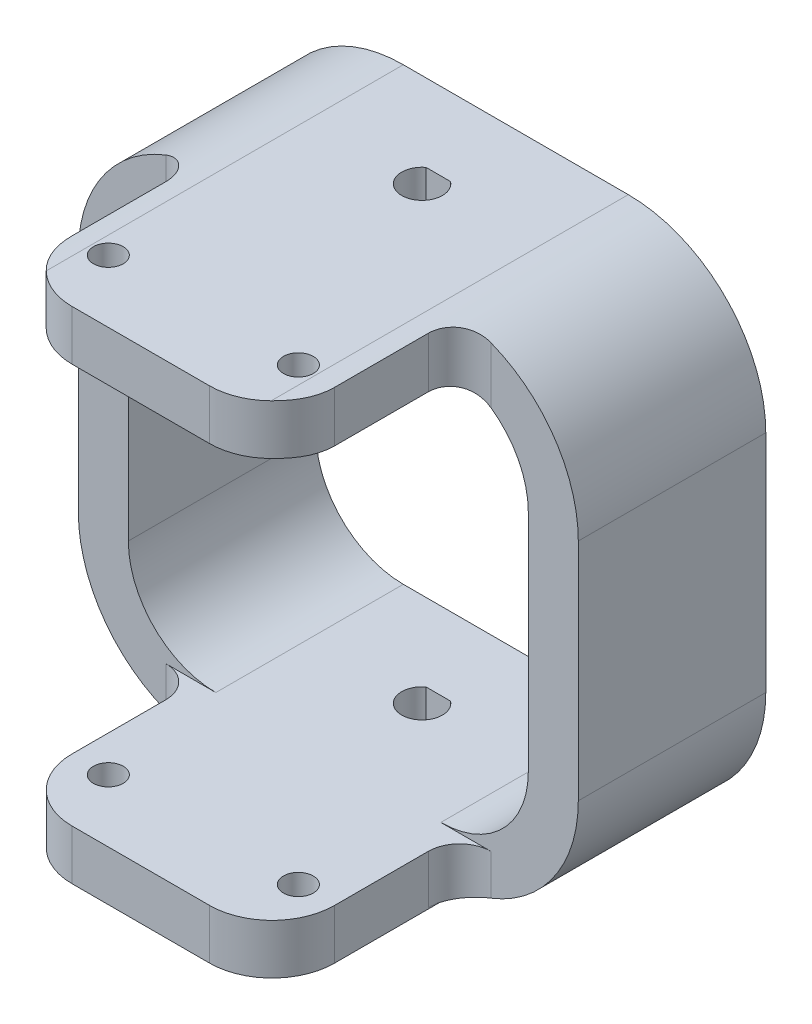
SolidWorks part; units mm, degrees
material "Plastique personnalisé"
ref_plane "Plan de face" through (0, 0, 0) normal (0, 0, 1) x (1, 0, 0)
ref_plane "Plan de dessus" through (0, 0, 0) normal (0, 1, 0) x (1, 0, 0)
ref_plane "Plan de droite" through (0, 0, 0) normal (1, 0, 0) x (0, 0, -1)
sketch "Esquisse1" plane through (0, 0, 0) normal (0, 0, 1) x (1, 0, 0)
  line L1 (40, -40) -> (-40, -40)
  line L2 (40, -40) -> (40, 40)
  line L3 (40, 40) -> (-40, 40)
  line L4 (-40, -40) -> (-40, 40)
  line L5 (40, -40) -> (-40, 40) construction
  line L6 (40, 40) -> (-40, -40) construction
  line L7 (-32, -32) -> (32, -32)
  line L8 (-32, -32) -> (-32, 32)
  line L9 (-32, 32) -> (32, 32)
  line L10 (32, -32) -> (32, 32)
  line L11 (-32, -32) -> (32, 32) construction
  line L12 (-32, 32) -> (32, -32) construction
  point P0 (0, 0)
  point P11 (0, 0)
  dimension "D1" = 8
  dimension "D3" = 80
extrude "Boss.-Extru.1" add sketch "Esquisse1" along normal mid plane 30
sketch "Esquisse2" plane through (0, 0, 0) normal (1, 0, 0) x (0, 0, -1)
  circle A0 centre (0, 0) radius 5
  dimension "D1" = 10
extrude "Enlèv. mat.-Extru.1" [suppressed] cut sketch "Esquisse2" against normal through all both and the other way through all
sketch "Esquisse3" plane through (0, -40, 0) normal (0, -1, 0) x (-1, 0, 0)
  circle A0 centre (0, 0) radius 5
  dimension "D1" = 10
extrude "Boss.-Extru.2" [suppressed] add sketch "Esquisse3" along normal blind 20
mirror "Symétrie1" [suppressed] about plane through (0, 0, 0) normal (0, 1, 0)
sketch "Esquisse7" plane through (0, 0, 15) normal (0, 0, 1) x (1, 0, 0)
  line L0 (40, 40) -> (-40, 40) construction
  line L1 (21, 32) -> (-21, 32)
  line L2 (21, 32) -> (21, 40)
  line L3 (21, 40) -> (-21, 40)
  line L4 (-21, 32) -> (-21, 40)
  line L5 (40, 40) -> (-40, 40) construction
  line L6 (32, 32) -> (-32, 32) construction
  point P10 (0, 40)
  point P11 (0, 40)
  dimension "D1" = 42
extrude "Boss.-Extru.4" add sketch "Esquisse7" along normal blind 30
fillet "Congé2" radius 22 4 edges at (40, -40, 0) (-40, -40, 0) (-40, 40, 0) (40, 40, 0)
fillet "Congé3" radius 14 4 edges at (-32, 32, 0) (-32, -32, 0) (32, -32, 0) (32, 32, 0)
sketch "Esquisse5" [suppressed] plane through (0, -60, 0) normal (0, -1, 0) x (1, 0, 0)
  circle A0 centre (0, 0) radius 3
  circle A1 centre (0, 0) radius 5 construction
  dimension "D1" = 6
extrude "Boss.-Extru.3" [suppressed] add sketch "Esquisse5" along normal blind 15
sketch "Esquisse6" [suppressed] plane through (0, -75, 0) normal (0, -1, 0) x (1, 0, 0)
  line L1 (3, -3) -> (-3, -3)
  line L2 (3, -3) -> (3, -1.8)
  line L3 (3, -1.8) -> (-3, -1.8)
  line L4 (-3, -3) -> (-3, -1.8)
  circle A0 centre (0, 0) radius 3 construction
  dimension "D1" = 1.2
extrude "Enlèv. mat.-Extru.2" [suppressed] cut sketch "Esquisse6" against normal up to surface (15 mm away) contours L1 L4 L3 L2 up to face at (0, -40, 0)
hole_wizard "Perçage pour écrous auto-bloquants 300® #6 (SP)1" positions "Esquisse10" profile "Esquisse9" hole size "#6-32" standard "PEM® Inch" end condition through all
sketch "Esquisse10" plane through (0, 40, 0) normal (0, -1, 0) x (0, 0, -1)
  line L0 (-35, 15.205) -> (-35, -15.205) construction
  line L3 (-35, 0) -> (-45, 0) construction
  line L6 (-45, 18) -> (-45, -18) construction
  point P0 (-35, 15.205)
  point P2 (-35, -15.205)
  point P20 (-45, 0)
  dimension "D1" = 30.41
  dimension "D2" = 10
sketch "Esquisse9" plane through (15.205, 40, 35) normal (1, 0, 0) x (0, 0, 1)
  line L0 (0, 0) -> (0, 80)
  line L1 (0, 80) -> (2.3812, 80)
  line L2 (2.3812, 80) -> (2.3812, 0)
  line L5 (2.3812, 0) -> (0, 0)
  line L11 (0, -6.35) -> (0, 107.95) construction
  dimension "Diamètre du perçage jusqu'au prochain" = 4.7625
  dimension "Profondeur du perçage jusqu'au prochain" = 80
fillet "Congé1" radius 10 2 edges at (21, 35.7346, 45) (-21, 35.7346, 45)
mirror "Symétrie2" about plane through (0, 0, 0) normal (0, 1, 0) of "Boss.-Extru.4", "Perçage pour écrous auto-bloquants 300® #6 (SP)1", "Congé1"
fillet "Congé4" radius 5 4 edges at (-21, -35.8972, 15) (-21, 35.7346, 15) (21, -35.8972, 15) (21, 35.7346, 15)
sketch "Esquisse11" plane through (0, -40, -40) normal (0, 1, 0) x (1, 0, 0)
  line L0 (40, -40) -> (-40, -40) construction
  line L1 (40, -25) -> (40, -55) construction
  line L2 (-40, -55) -> (-40, -25) construction
  line L3 (1.9649, -37.405) -> (-1.9649, -37.405)
  arc A0 (-1.9649, -37.405) -> (1.9649, -37.405) centre (0, -40) ccw
  dimension "D1" = 6.51
  dimension "D2" = 5.85
extrude "Enlèv. mat.-Extru.3" cut sketch "Esquisse11" along normal through all
